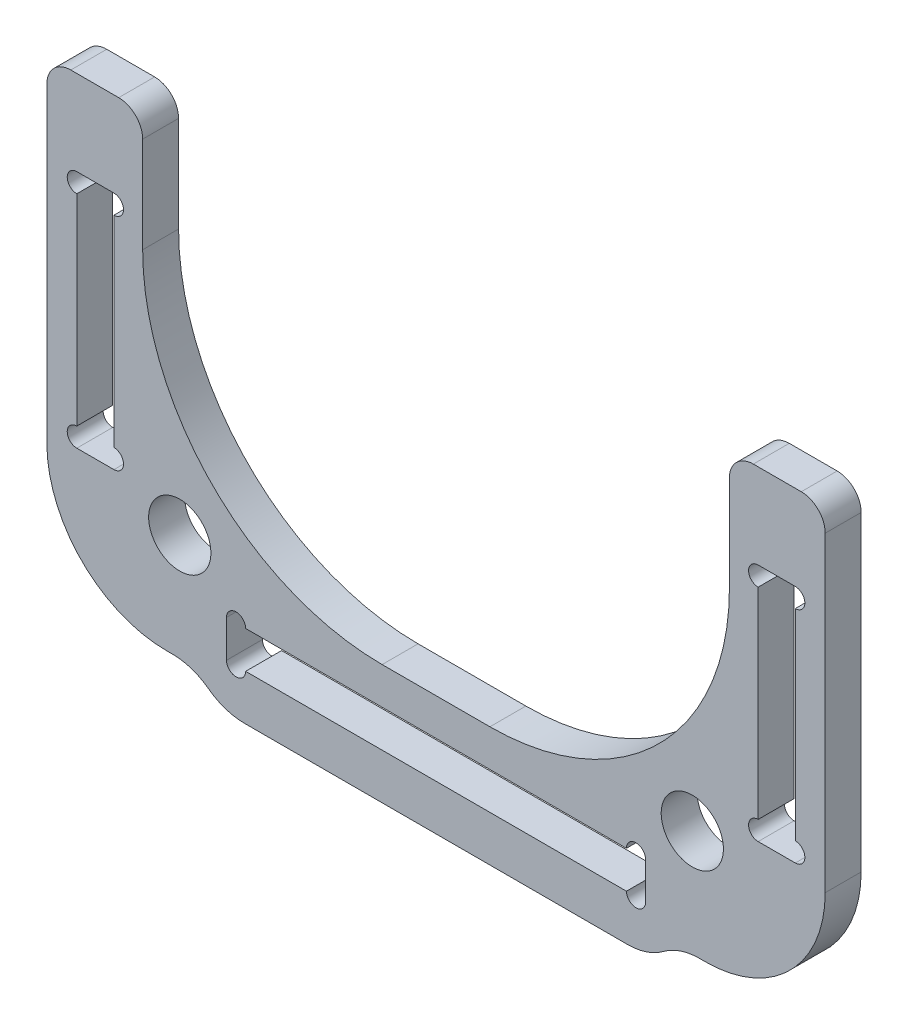
SolidWorks part; units mm, degrees
material "Thornel Mat VMA"
ref_plane "Front Plane" through (0, 0, 0) normal (0, 0, 1) x (1, 0, 0)
ref_plane "Top Plane" through (0, 0, 0) normal (0, 1, 0) x (1, 0, 0)
ref_plane "Right Plane" through (0, 0, 0) normal (1, 0, 0) x (0, 0, -1)
sketch "Sketch1" plane through (0, 0, 0) normal (0, 0, 1) x (1, 0, 0)
  line L0 (0, 0) -> (0, 8) construction
  line L1 (0, 0) -> (-32.5, 0)
  line L2 (-32.5, 0) -> (-32.5, 38)
  line L3 (0, 8) -> (-24.5, 8)
  line L4 (-24.5, 8) -> (-24.5, 38)
  line L5 (0, 0) -> (0, 8) construction
  line L6 (-32.5, 38) -> (-24.5, 38)
  line L7 (0, 0) -> (32.5, 0)
  line L8 (0, 8) -> (24.5, 8)
  line L9 (32.5, 38) -> (24.5, 38)
  line L10 (24.5, 8) -> (24.5, 38)
  line L11 (32.5, 0) -> (32.5, 38)
  dimension "D1" = 65
  dimension "D3" = 30
  dimension "D2" = 8
extrude "Boss-Extrude1" add sketch "Sketch1" along normal blind 3
fillet "Fillet1" radius 20 2 edges at (24.5, 8, 1.5) (-24.5, 8, 1.5)
sketch "Sketch2" plane through (0, 0, 3) normal (0, 0, 1) x (1, 0, 0)
  line L0 (-28.45, 38) -> (-28.45, 0) construction
  line L1 (-24.5, 38) -> (-32.5, 38) construction
  line L2 (-32.5, 0) -> (32.5, 0) construction
  line L3 (-32.5, 38) -> (-32.5, 0) construction
  line L4 (-30, 10.9) -> (-26.9, 10.9)
  line L5 (-30, 12.5) -> (-30, 29.3)
  line L6 (-30, 30.9) -> (-26.9, 30.9)
  line L7 (-26.9, 12.5) -> (-26.9, 29.3)
  line L8 (-30, 10.9) -> (-26.9, 30.9) construction
  line L9 (-30, 30.9) -> (-26.9, 10.9) construction
  line L10 (0, 0) -> (0, 6.72) construction
  line L12 (30, 30.9) -> (26.9, 10.9) construction
  line L13 (30, 10.9) -> (26.9, 30.9) construction
  line L14 (28.45, 38) -> (28.45, 0) construction
  line L15 (26.9, 12.5) -> (26.9, 29.3)
  line L16 (30, 30.9) -> (26.9, 30.9)
  line L17 (30, 12.5) -> (30, 29.3)
  line L18 (30, 10.9) -> (26.9, 10.9)
  line L20 (-15.9, 1.81) -> (15.9, 1.81)
  line L21 (-17.5, 1.81) -> (-17.5, 4.91)
  line L22 (-15.9, 4.91) -> (15.9, 4.91)
  line L23 (17.5, 1.81) -> (17.5, 4.91)
  line L24 (-17.5, 1.81) -> (17.5, 4.91) construction
  line L25 (-17.5, 4.91) -> (17.5, 1.81) construction
  arc A0 (-30, 30.9) -> (-30, 29.3) centre (-30, 30.1) ccw
  arc A1 (-26.9, 29.3) -> (-26.9, 30.9) centre (-26.9, 30.1) ccw
  arc A2 (-30, 12.5) -> (-30, 10.9) centre (-30, 11.7) ccw
  arc A3 (-26.9, 10.9) -> (-26.9, 12.5) centre (-26.9, 11.7) ccw
  arc A4 (26.9, 10.9) -> (26.9, 12.5) centre (26.9, 11.7) cw
  arc A5 (30, 12.5) -> (30, 10.9) centre (30, 11.7) cw
  arc A6 (26.9, 29.3) -> (26.9, 30.9) centre (26.9, 30.1) cw
  arc A7 (30, 30.9) -> (30, 29.3) centre (30, 30.1) cw
  arc A8 (-15.9, 4.91) -> (-17.5, 4.91) centre (-16.7, 4.91) ccw
  arc A9 (-17.5, 1.81) -> (-15.9, 1.81) centre (-16.7, 1.81) ccw
  arc A10 (17.5, 4.91) -> (15.9, 4.91) centre (16.7, 4.91) ccw
  arc A11 (15.9, 1.81) -> (17.5, 1.81) centre (16.7, 1.81) ccw
  point P6 (-28.45, 20.9)
  point P40 (28.45, 20.9)
  point P41 (0, 3.36)
  point P51 (0, 0)
  dimension "D4" = 1.6
  dimension "D7" = 1.6
  dimension "D1" = 20
  dimension "D2" = 2.5
  dimension "D3" = 3.1
  dimension "D5" = 3.1
  dimension "D6" = 35
  dimension "D8" = 7.1
  dimension "D9" = 1.81
extrude "Cut-Extrude1" cut sketch "Sketch2" against normal through all
sketch "Sketch3" plane through (0, 0, 3) normal (0, 0, 1) x (1, 0, 0)
  line L0 (-26.9, 12.5) -> (-26.9, 29.3) construction
  line L1 (15.9, 4.91) -> (-15.9, 4.91) construction
  line L2 (0, 0) -> (0, 8) construction
  line L3 (4.5, 8) -> (-4.5, 8) construction
  circle A1 centre (-21.4, 8.91) radius 2.6
  circle A2 centre (21.4, 8.91) radius 2.6
  dimension "D1" = 5.2
  dimension "D2" = 5.5
  dimension "D3" = 4
extrude "Cut-Extrude2" cut sketch "Sketch3" against normal through all
fillet "Fillet2" radius 10 2 edges at (-32.5, 0, 1.5) (32.5, 0, 1.5)
fillet "Fillet3" radius 2 4 edges at (-32.5, 38, 1.5) (-24.5, 38, 1.5) (24.5, 38, 1.5) (32.5, 38, 1.5)
sketch "Sketch4" plane through (0, 0, 3) normal (0, 0, 1) x (1, 0, 0)
  line L0 (-22.5, 0) -> (22.5, 0) construction
  line L1 (-18, 0) -> (18, 0)
  line L2 (-18, 0) -> (-18, -2)
  line L3 (-18, -2) -> (18, -2)
  line L4 (18, 0) -> (18, -2)
  line L5 (0, -2) -> (0, 0) construction
  dimension "D1" = 2
  dimension "D2" = 36
extrude "Boss-Extrude2" add sketch "Sketch4" against normal up to surface (3 mm away) up to face at (-18.8, 8.91, 0)
fillet "Fillet4" radius 5 2 edges at (18, 0, 1.5) (-18, 0, 1.5)
fillet "Fillet5" radius 5 2 edges at (-18, -2, 1.5) (18, -2, 1.5)
